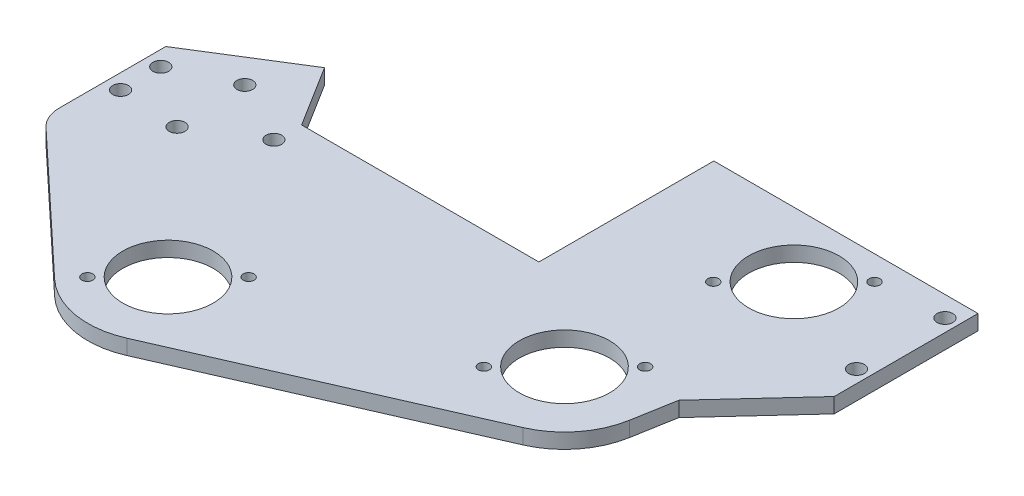
SolidWorks part; units mm, degrees
material "6061 Alloy"
ref_plane "Front Plane" through (0, 0, 0) normal (0, 0, 1) x (1, 0, 0)
ref_plane "Top Plane" through (0, 0, 0) normal (0, 1, 0) x (1, 0, 0)
ref_plane "Right Plane" through (0, 0, 0) normal (1, 0, 0) x (0, 0, -1)
sketch "Sketch1" plane through (0, 0, 0) normal (0, 1, 0) x (1, 0, 0)
  line L1 (-62.0382, -79.8833) -> (25.1671, -41.6958)
  line L5 (39.9402, -22.8907) -> (42.2751, -9.5867)
  line L6 (42.2751, -9.5867) -> (65.831, 16.0128)
  line L12 (-135.7544, -31.9237) -> (-135.7544, 6.1763)
  line L16 (-92.7762, 6.1643) -> (-17.7344, 6.1643)
  line L17 (-135.7544, -31.9237) -> (-89.5888, -75.1562)
  line L19 (65.831, 61.4936) -> (-17.7344, 61.4936)
  line L20 (65.831, 16.0128) -> (65.831, 61.4936)
  line L22 (-17.7344, 61.4936) -> (-17.7344, 6.1643)
  line L23 (-135.7544, 6.1763) -> (-104.8504, 25.4872)
  line L24 (-218.6325, 207.5765) -> (-71.6498, -27.6449) construction
  line L25 (-104.8504, 25.4872) -> (-92.7762, 6.1643)
  line L26 (-72.2583, -56.6285) -> (15.031, -18.5085) construction
  line L27 (-72.2269, -82.0164) -> (109.3231, -82.0164) construction
  line L28 (15.0167, -18.5164) -> (15.0167, -82.0164) construction
  circle A0 centre (28.0466, 41.0458) radius 14.29
  circle A1 centre (15.031, -18.5085) radius 14.29
  circle A2 centre (-72.2583, -56.6285) radius 14.29
  arc A4 (39.9402, -22.8907) -> (25.1671, -41.6958) centre (15.0167, -18.5164) cw
  arc A6 (-62.0382, -79.8833) -> (-89.5888, -75.1562) centre (-72.2269, -56.6164) cw
  circle A7 centre (15.031, -18.5085) radius 25.4 construction
  circle A8 centre (-72.2583, -56.6285) radius 25.4 construction
  circle A9 centre (-28.6137, -37.5685) radius 22.225 construction
  circle A10 centre (28.0466, 41.0458) radius 30.48 construction
  circle A11 centre (15.031, -18.5085) radius 30.48 construction
  point P11 (-62.0382, -79.8833)
  point P34 (15.0167, -18.5164)
  point P35 (28.0466, 41.0458)
  dimension "D2" = 50.8
  dimension "D3" = 50.8
  dimension "D4" = 44.45
  dimension "D5" = 63.5
  dimension "D7" = 60.96
  dimension "D8" = 60.96
  dimension "D1" = 140.0048
  dimension "D6" = 95.25
  dimension "D9" = 50.8
  dimension "D10" = 143.51
extrude "Boss-Extrude1" add sketch "Sketch1" along normal blind 4.7625
fillet "Fillet1" radius 10 1 edges at (-135.7544, 2.3813, 31.9237)
hole_wizard "#10 Clearance Hole1" positions "Sketch2" profile "Sketch3" hole size "#10" standard "ANSI Inch" end condition through all
sketch "Sketch2" plane through (0, 4.7625, 0) normal (0, 1, 0) x (1, 0, 0)
  point P0 (61.8305, 55.0158)
  point P3 (61.8305, 27.0758)
  point P7 (-130.9919, -0.1857)
  point P10 (-130.9919, -12.8857)
sketch "Sketch3" plane through (61.8305, 4.7625, -55.0158) normal (1, 0, 0) x (0, 0, 1)
  line L0 (0, 0) -> (0, 4.7625)
  line L1 (0, 4.7625) -> (2.4892, 4.7625)
  line L2 (2.4892, 4.7625) -> (2.4892, 0)
  line L5 (2.4892, 0) -> (0, 0)
  line L11 (0, -6.35) -> (0, 107.95) construction
  dimension "Thru Hole Dia." = 4.9784
  dimension "Thru Hole Depth" = 4.7625
sketch "Sketch4" plane through (0, 4.7625, 0) normal (0, 1, 0) x (1, 0, 0)
  line L0 (-72.2583, -56.6285) -> (-102.5432, -8.1625) construction
  line L1 (-102.5432, -8.1625) -> (-93.1193, -2.2738) construction
  line L2 (-102.5432, -8.1625) -> (-111.9672, -14.0512) construction
  line L3 (-102.5432, -8.1625) -> (-112.7324, 8.1436) construction
  line L4 (-102.5432, -8.1625) -> (-174.2713, 106.6264) construction
  line L5 (65.831, 41.0458) -> (65.831, 28.3458) construction
  dimension "D1" = 57.15
  dimension "D2" = 22.225
  dimension "D3" = 32
hole_wizard "#10 Clearance Hole2" positions "Sketch5" profile "Sketch6" hole size "#10" standard "ANSI Inch" end condition through all
sketch "Sketch5" plane through (0, 4.7625, 0) normal (0, 1, 0) x (1, 0, 0)
  point P0 (-111.9672, -14.0512)
  point P3 (-93.1193, -2.2738)
  point P7 (-112.7324, 8.1436)
sketch "Sketch6" plane through (-111.9672, 4.7625, 14.0512) normal (1, 0, 0) x (0, 0, 1)
  line L0 (0, 0) -> (0, 4.7625)
  line L1 (0, 4.7625) -> (2.4892, 4.7625)
  line L2 (2.4892, 4.7625) -> (2.4892, 0)
  line L5 (2.4892, 0) -> (0, 0)
  line L11 (0, -6.35) -> (0, 107.95) construction
  dimension "Thru Hole Dia." = 4.9784
  dimension "Thru Hole Depth" = 4.7625
sketch "Sketch7" plane through (0, 4.7625, 0) normal (0, 1, 0) x (1, 0, 0)
  line L0 (-85.0103, -69.3804) -> (-59.5064, -43.8765) construction
  line L1 (2.279, -31.2604) -> (27.783, -5.7565) construction
  line L3 (15.2946, 28.2939) -> (40.7985, 53.7978) construction
  point P7 (-72.2583, -56.6285)
  point P11 (15.031, -18.5085)
  point P13 (28.0466, 41.0458)
hole_wizard "Tap Drill for #8-32 Tap1" positions "Sketch8" profile "Sketch9" hole size "#8-32" standard "ANSI Inch" end condition through all
sketch "Sketch8" plane through (0, 4.7625, 0) normal (0, 1, 0) x (1, 0, 0)
  point P0 (-59.5064, -43.8765)
  point P3 (-85.0103, -69.3804)
  point P6 (2.279, -31.2604)
  point P9 (27.783, -5.7565)
  point P12 (15.2946, 28.2939)
  point P15 (40.7985, 53.7978)
sketch "Sketch9" plane through (-59.5064, 4.7625, 43.8765) normal (1, 0, 0) x (0, 0, 1)
  line L0 (0, 0) -> (0, 4.7625)
  line L1 (0, 4.7625) -> (1.7272, 4.7625)
  line L2 (1.7272, 4.7625) -> (1.7272, 0)
  line L5 (1.7272, 0) -> (0, 0)
  line L11 (0, -6.35) -> (0, 107.95) construction
  dimension "Thru Hole Dia." = 3.4544
  dimension "Thru Hole Depth" = 4.7625
